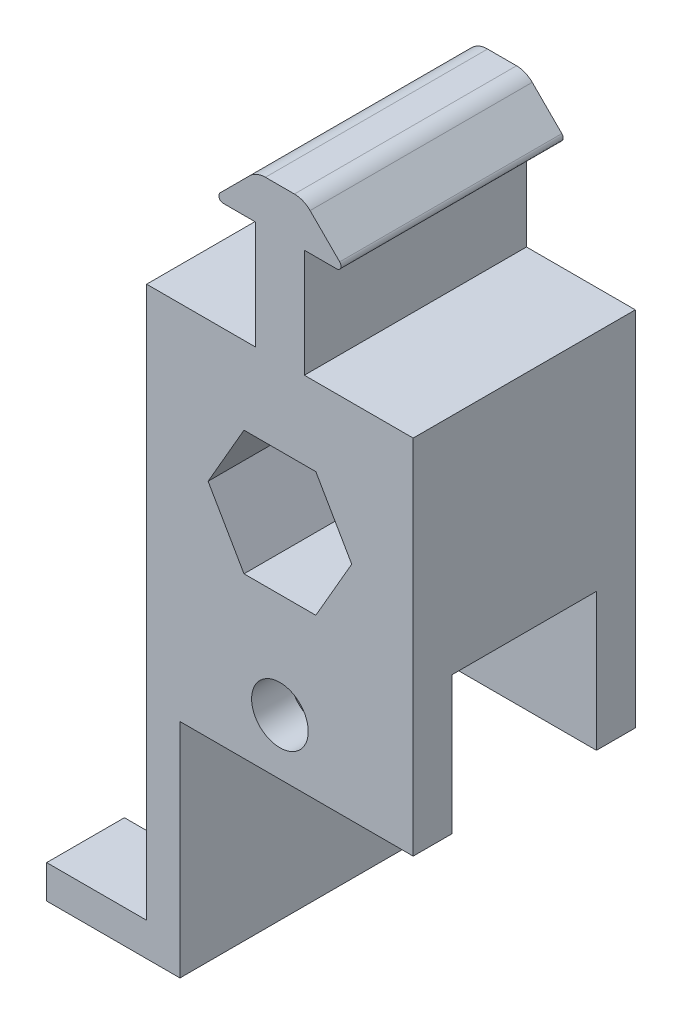
SolidWorks part; units mm, degrees
ref_plane "Front Plane" through (0, 0, 0) normal (0, 0, 1) x (1, 0, 0)
ref_plane "Top Plane" through (0, 0, 0) normal (0, 1, 0) x (1, 0, 0)
ref_plane "Right Plane" through (0, 0, 0) normal (1, 0, 0) x (0, 0, -1)
sketch "Sketch1" plane through (0, 0, 0) normal (0, 0, 1) x (1, 0, 0)
  line L0 (-15.24, 16.002) -> (-15.24, -25.4)
  line L1 (-4.1061, 7.112) -> (-8.2122, 0)
  line L2 (-8.2122, 0) -> (-4.1061, -7.112)
  line L3 (-4.1061, -7.112) -> (4.1061, -7.112)
  line L4 (4.1061, -7.112) -> (8.2122, 0)
  line L5 (8.2122, 0) -> (4.1061, 7.112)
  line L6 (4.1061, 7.112) -> (-4.1061, 7.112)
  line L7 (-15.24, -25.4) -> (15.24, -25.4)
  line L8 (15.24, -25.4) -> (15.24, 16.002)
  line L9 (-15.24, 16.002) -> (-2.794, 16.002)
  line L10 (-2.794, 16.002) -> (-2.794, 28.3845)
  line L11 (-2.794, 28.3845) -> (-6.477, 28.3845)
  line L12 (-6.8362, 29.2517) -> (-3.4525, 32.6355)
  line L13 (-1.6564, 33.3794) -> (1.6564, 33.3794)
  line L14 (0, 41.8096) -> (0, -25.778) construction
  line L15 (15.24, 16.002) -> (2.794, 16.002)
  line L16 (2.794, 16.002) -> (2.794, 28.3845)
  line L17 (6.8362, 29.2517) -> (3.4525, 32.6355)
  line L18 (2.794, 28.3845) -> (6.477, 28.3845)
  line L19 (-6.985, 28.8925) -> (6.985, 28.8925) construction
  circle A0 centre (0, 0) radius 7.112 construction
  arc A1 (-6.477, 28.3845) -> (-6.8362, 29.2517) centre (-6.477, 28.8925) cw
  arc A2 (-3.4525, 32.6355) -> (-1.6564, 33.3794) centre (-1.6564, 30.8394) cw
  arc A3 (3.4525, 32.6355) -> (1.6564, 33.3794) centre (1.6564, 30.8394) ccw
  arc A4 (6.477, 28.3845) -> (6.8362, 29.2517) centre (6.477, 28.8925) ccw
  point P18 (7.7034, 28.3845)
  point P21 (-4.6355, 28.3845)
  point P25 (-7.7034, 28.3845)
  point P29 (0, -25.4)
  point P35 (0, 33.3794)
  dimension "D7" = 0.508
  dimension "D8" = 2.54
  dimension "D1" = 14.224
  dimension "D2" = 21.2725
  dimension "D3" = 5.588
  dimension "D4" = 4.9949
  dimension "D5" = 135
  dimension "D6" = 13.97
  dimension "D9" = 25.4
  dimension "D10" = 8.89
  dimension "D11" = 15.24
extrude "Boss-Extrude1" add sketch "Sketch1" along normal mid plane 25.4
sketch "Sketch10" plane through (0, 0, 0) normal (0, 0, 1) x (1, 0, 0)
  line L0 (-15.24, -25.4) -> (-15.24, -46.99)
  line L1 (-15.24, -46.99) -> (-26.67, -46.99)
  line L2 (-26.67, -46.99) -> (-26.67, -50.8)
  line L3 (-26.67, -50.8) -> (-11.43, -50.8)
  line L4 (-11.43, -50.8) -> (-11.43, -25.4)
  line L5 (-15.24, -25.4) -> (15.24, -25.4) construction
  line L6 (-15.24, -25.4) -> (-11.43, -25.4)
  dimension "D2" = 21.59
  dimension "D3" = 3.81
  dimension "D4" = 11.43
extrude "Boss-Extrude4" add sketch "Sketch10" along normal up to surface and the other way up to surface up to face at (0, 19.8373, 12.7) other way up to face at (0, 19.8373, -12.7)
sketch "Sketch6" plane through (15.24, 0, 0) normal (1, 0, 0) x (0, 0, -1)
  line L0 (-12.7, -7.112) -> (12.7, -7.112) construction
  line L1 (-12.7, -7.112) -> (12.7, -7.112) construction
  line L2 (-8.255, -25.4) -> (-8.255, -9.652)
  line L3 (-8.255, -9.652) -> (8.255, -9.652)
  line L11 (-8.255, -25.4) -> (8.255, -25.4)
  line L12 (8.255, -9.652) -> (8.255, -25.4)
  point P10 (0, -9.652)
  dimension "D2" = 16.51
  dimension "D3" = 2.54
  dimension "D1" = 15.748
extrude "Cut-Extrude2" cut sketch "Sketch6" against normal through all
sketch "Sketch11" plane through (0, -46.99, 0) normal (0, 1, 0) x (1, 0, 0)
  line L0 (-26.67, -12.7) -> (-26.67, 12.7) construction
  line L1 (-15.24, -12.7) -> (-15.24, 12.7) construction
  line L2 (-26.67, -3.81) -> (-26.67, 3.81)
  line L3 (-15.24, -3.81) -> (-15.24, 3.81)
  line L4 (-26.67, 3.81) -> (-15.24, 3.81)
  line L5 (-26.67, -3.81) -> (-15.24, -3.81)
  point P8 (-15.24, 0)
  point P9 (-26.67, 0)
  dimension "D1" = 7.62
extrude "Cut-Extrude3" cut sketch "Sketch11" against normal up to surface (3.81 mm away) up to face at (-19.05, -50.8, 0)
sketch "Sketch15" plane through (0, 0, 12.7) normal (0, 0, 1) x (1, 0, 0)
  line L1 (-4.1061, -7.112) -> (4.1061, -7.112) construction
  circle A0 centre (0, -19.05) radius 3.2385
  point P7 (0, -7.112)
  dimension "D1" = 6.477
  dimension "D2" = 11.938
extrude "Cut-Extrude4" cut sketch "Sketch15" against normal up to surface (25.4 mm away) up to face at (-3.81, 6.0908, -12.7)
